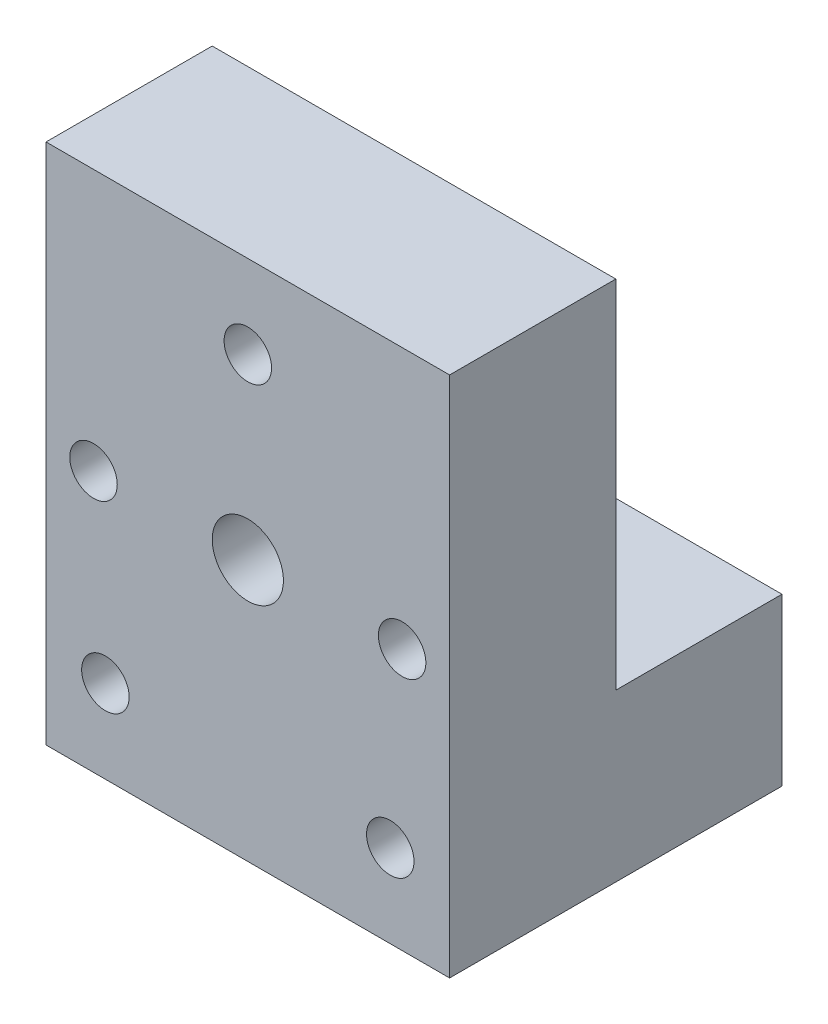
SolidWorks part; units mm, degrees
ref_plane "Front Plane" through (0, 0, 0) normal (0, 0, 1) x (1, 0, 0)
ref_plane "Top Plane" through (0, 0, 0) normal (0, 1, 0) x (1, 0, 0)
ref_plane "Right Plane" through (0, 0, 0) normal (1, 0, 0) x (0, 0, -1)
sketch "Sketch1" plane through (0, 0, 0) normal (0, 0, 1) x (1, 0, 0)
  line L1 (-107.95, 50.8) -> (107.95, 50.8)
  line L2 (-107.95, 50.8) -> (-107.95, -50.8)
  line L3 (-107.95, -50.8) -> (107.95, -50.8)
  line L4 (107.95, 50.8) -> (107.95, -50.8)
  line L5 (-107.95, 50.8) -> (107.95, -50.8) construction
  line L6 (-107.95, -50.8) -> (107.95, 50.8) construction
  line L7 (-107.95, -139.7) -> (107.95, -139.7)
  line L8 (-107.95, -139.7) -> (-107.95, -50.8)
  line L9 (-107.95, -50.8) -> (107.95, -50.8)
  line L10 (107.95, -139.7) -> (107.95, -50.8)
  line L11 (-107.95, -139.7) -> (107.95, -50.8) construction
  line L12 (-107.95, -50.8) -> (107.95, -139.7) construction
  circle A0 centre (-82.55, 0) radius 12.7
  circle A1 centre (82.55, 0) radius 12.7
  point P0 (0, 0)
  point P6 (0, -95.25)
  point P11 (0, 0)
  point P14 (47.3476, 12.2242)
  point P15 (0, 0)
  dimension "D3" = 25.4
  dimension "D1" = 101.6
  dimension "D2" = 88.9
  dimension "D4" = 25.4
  dimension "D5" = 25.4
  dimension "D6" = 215.9
extrude "Boss-Extrude1" add sketch "Sketch1" along normal blind 88.9 contours L4 L1 L2 L3 A1 A0 | L7 L10 L3 L8 region at (0, 0, 0) region at (0, -95.25, 0)
extrude "Boss-Extrude2" add sketch "Sketch1<3>" against normal blind 88.9 contours L7 L10 L3 L8 region at (0, -95.25, 0)
sketch "Sketch1<3>" plane through (0, 0, 0) normal (0, 0, 1) x (1, 0, 0) same geometry as "Sketch1"
sketch "Sketch2" plane through (0, 0, 88.9) normal (0, 0, 1) x (1, 0, 0)
  line L0 (-107.95, -139.7) -> (107.95, -139.7) construction
  line L1 (-107.95, 139.7) -> (107.95, 139.7)
  line L2 (-107.95, 139.7) -> (-107.95, 50.8)
  line L3 (-107.95, 50.8) -> (107.95, 50.8)
  line L4 (107.95, 139.7) -> (107.95, 50.8)
  line L5 (-107.95, 139.7) -> (107.95, 50.8) construction
  line L6 (-107.95, 50.8) -> (107.95, 139.7) construction
  line L7 (-76.2, -95.25) -> (76.2, -95.25) construction
  circle A0 centre (0, 0) radius 19.05
  circle A1 centre (0, -95.25) radius 12.7
  circle A2 centre (0, 95.25) radius 12.7
  circle A3 centre (76.2, -95.25) radius 12.7
  circle A4 centre (-76.2, -95.25) radius 12.7
  point P19 (0, -95.25)
  line M5 (107.95, 50.8) -> (-107.95, 50.8)
  dimension "D1" = 38.1
  dimension "D2" = 25.4
  dimension "D5" = 152.4
  dimension "D3" = 44.45
  dimension "D4" = 44.45
extrude "Boss-Extrude3" add sketch "Sketch2" against normal up to surface (88.9 mm away) contours L4 L1 L2 A2 M5 region at (0, 137.3651, 88.9) up to face at (-69.85, 0, 0)
extrude "Cut-Extrude1" cut sketch "Sketch2<3>" against normal up to next contours A4 | A3 | A0 region at (0, 0, 88.9) region at (76.2, -95.25, 88.9) region at (-76.2, -95.25, 88.9)
sketch "Sketch2<3>" plane through (0, 0, 88.9) normal (0, 0, 1) x (1, 0, 0) same geometry as "Sketch2"
